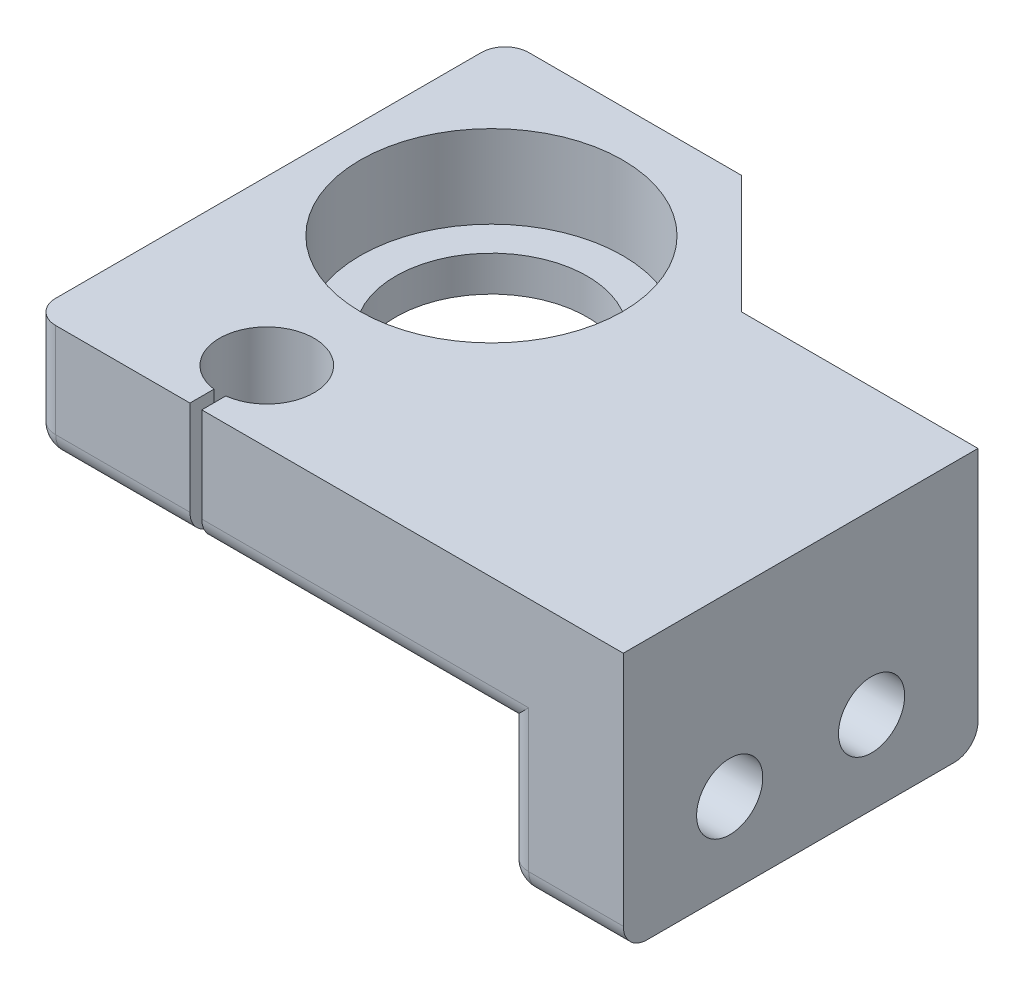
SolidWorks part; units mm, degrees
ref_plane "Front Plane" through (0, 0, 0) normal (0, 0, 1) x (1, 0, 0)
ref_plane "Top Plane" through (0, 0, 0) normal (0, 1, 0) x (1, 0, 0)
ref_plane "Right Plane" through (0, 0, 0) normal (1, 0, 0) x (0, 0, -1)
sketch "Sketch1" plane through (0, 0, 0) normal (0, 1, 0) x (1, 0, 0)
  line L0 (13.85, -15) -> (13.85, -34) construction
  line L1 (0, 0) -> (50, 0)
  line L2 (0, 0) -> (0, -40)
  line L3 (0, -40) -> (50, -40)
  line L4 (50, 0) -> (50, -40)
  line L5 (13.85, -34) -> (13.85, -40) construction
  line L6 (13.85, -15) -> (13.85, 0) construction
  line L8 (13.35, -37.9686) -> (14.35, -37.9686)
  line L9 (13.35, -37.9686) -> (13.35, -40)
  line L10 (13.35, -40) -> (14.35, -40)
  line L11 (14.35, -37.9686) -> (14.35, -40)
  circle A0 centre (13.85, -34) radius 4
  circle A1 centre (13.85, -15) radius 8.1
  circle A2 centre (13.85, -15) radius 11.1 construction
  dimension "D3" = 8
  dimension "D4" = 6
  dimension "D6" = 22.2
  dimension "D7" = 3
  dimension "D1" = 40
  dimension "D2" = 50
  dimension "D5" = 19
  dimension "D8" = 1
  dimension "D9" = 13.85
extrude "Boss-Extrude1" add sketch "Sketch1" along normal blind 10 contours A0 L1 L2 L3 L4 A1 region at (26.6543, 0, 20.1658)
sketch "Sketch2" plane through (0, 10, 0) normal (0, 1, 0) x (1, 0, 0)
  circle A0 centre (13.85, -15) radius 11.1 construction
  circle A1 centre (13.85, -15) radius 11.1
extrude "Cut-Extrude1" cut sketch "Sketch2" against normal blind 7
sketch "Sketch6" plane through (0, 0, 40) normal (0, 0, 1) x (1, 0, 0)
  line L1 (50, 0) -> (40, 0)
  line L2 (50, 0) -> (50, -12)
  line L3 (50, -12) -> (40, -12)
  line L4 (40, 0) -> (40, -12)
  dimension "D1" = 12
  dimension "D2" = 10
extrude "Boss-Extrude3" add sketch "Sketch6" against normal blind 30
sketch "Sketch7" plane through (40, 0, 0) normal (-1, 0, 0) x (0, 0, 1)
  line L0 (31, -5) -> (19, -5) construction
  line L1 (19, -5) -> (10, -5) construction
  line L2 (10, 0) -> (10, -12) construction
  line L3 (31, -5) -> (40, -5) construction
  line L4 (40, 0) -> (40, -12) construction
  line L5 (10, 0) -> (40, 0) construction
  circle A0 centre (19, -5) radius 2.8
  circle A1 centre (31, -5) radius 2.8
  dimension "D1" = 12
  dimension "D3" = 5.6
  dimension "D2" = 5
extrude "Cut-Extrude2" cut sketch "Sketch7" against normal through all
sketch "Sketch8" plane through (40, 0, 0) normal (-1, 0, 0) x (0, 0, 1)
  circle A0 centre (19, -5) radius 4.3
  circle A1 centre (31, -5) radius 4.3
  dimension "D1" = 8.6
extrude "Cut-Extrude3" cut sketch "Sketch8" against normal blind 6
fillet "Fillet1" radius 2 11 edges at (45, -12, 10) (45, -12, 40) (6.675, 0, 40) (27.175, 0, 40) (40, -6, 40) (40, -12, 25) (40, -6, 10) (0, 5, 40) (0, 5, 0) (25, 0, 0) (0, 0, 20)
sketch "Sketch9" plane through (0, 0, 0) normal (0, -1, 0) x (1, 0, 0)
  line L0 (50, 0) -> (2, 0) construction
  line L1 (50, 10) -> (30, 10)
  line L2 (50, 10) -> (50, 0)
  line L3 (50, 0) -> (30, 0)
  line L4 (30, 10) -> (30, 0)
  dimension "D1" = 20
extrude "Cut-Extrude4" cut sketch "Sketch9" against normal through all
sketch "Sketch10" plane through (0, 10, 0) normal (0, 1, 0) x (1, 0, 0)
  line L0 (30, 0) -> (20, 0)
  line L1 (2, 0) -> (30, 0) construction
  line L2 (20, 0) -> (30, -10)
  line L3 (30, -10) -> (30, 0) construction
  line L4 (30, -10) -> (30, 0)
  dimension "D1" = 10
extrude "Cut-Extrude5" cut sketch "Sketch10" against normal through all
